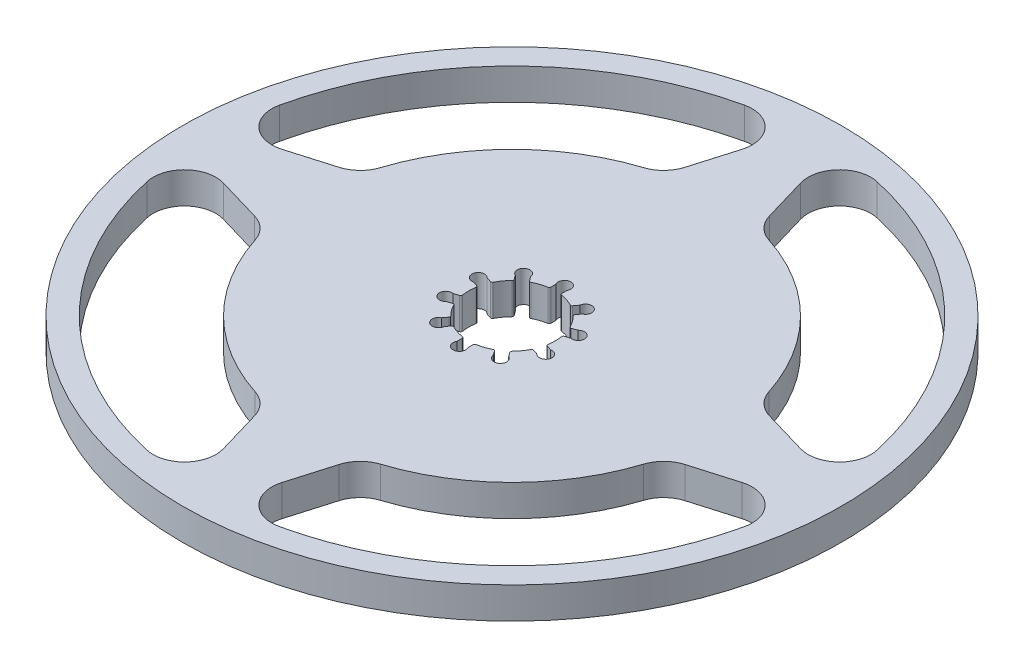
SolidWorks part; units mm, degrees
material "Alum Plate"
ref_plane "Front Plane" through (0, 0, 0) normal (0, 0, 1) x (1, 0, 0)
ref_plane "Top Plane" through (0, 0, 0) normal (0, 1, 0) x (1, 0, 0)
ref_plane "Right Plane" through (0, 0, 0) normal (1, 0, 0) x (0, 0, -1)
other "Center of Mass"
other "Bounding Box"
ref_plane "Default Plane" through (0, 2.286, 19.05) normal (0, -1, 0) x (-1, 0, 0)
sketch "Sketch1" plane through (0, 0, 0) normal (0, 1, 0) x (1, 0, 0)
  circle A0 centre (0, 0) radius 133.35 construction
  circle A1 centre (0, 0) radius 82.55
  circle A2 centre (0, 0) radius 17.4625
  dimension "D1" = 266.7
  dimension "D2" = 165.1
  dimension "D3" = 34.925
extrude "Boss-Extrude1" add sketch "Sketch1" along normal mid plane 12.7
sketch "Sketch8" plane through (0, 6.35, 0) normal (0, 1, 0) x (1, 0, 0)
  circle A0 centre (0, 0) radius 123.825
  circle A1 centre (0, 0) radius 133.35
  circle A2 centre (0, 0) radius 133.35 construction
  dimension "D1" = 9.525
extrude "Boss-Extrude4" add sketch "Sketch8" against normal through all
sketch "Sketch2" plane through (0, 6.35, 0) normal (0, 1, 0) x (1, 0, 0)
  line L4 (0, 0) -> (0, 133.35) construction
  line L6 (-6.35, 123.6621) -> (6.35, 123.6621) construction
  line L7 (-6.35, 123.6621) -> (-19.05, 80.3219)
  line L8 (-19.05, 80.3219) -> (19.05, 80.3219)
  line L9 (6.35, 123.6621) -> (19.05, 80.3219)
  line L10 (-6.35, 123.6621) -> (19.05, 80.3219) construction
  line L11 (-19.05, 80.3219) -> (6.35, 123.6621) construction
  circle A5 centre (0, 0) radius 133.35 construction
  circle A7 centre (0, 0) radius 82.55 construction
  arc A9 (-6.35, 123.6621) -> (6.35, 123.6621) centre (0, 0) cw
  circle A10 centre (0, 0) radius 123.825 construction
  point P4 (0, 112.827)
  point P6 (13.7165, 123.0629)
  point P11 (-14.1161, 122.0628)
  point P13 (6.9138, 120.4517)
  dimension "D1" = 38.1
  dimension "D2" = 12.7
extrude "Boss-Extrude2" add sketch "Sketch2" against normal through all
fillet "Fillet7" radius 12.7 4 edges at (-6.35, 0, -123.6621) (-19.05, 0, -80.3219) (19.05, 0, -80.3219) (6.35, 0, -123.6621)
pattern_circular "CirPattern5" count 4 over 360 about axis through (0, 6.35, 0) along (0, -1, 0) of "Boss-Extrude2", "Fillet7"
sketch "Sketch5" plane through (0, 6.35, 0) normal (0, 1, 0) x (1, 0, 0)
  line L0 (0, 17.4625) -> (0, 21.2725) construction
  line L2 (-2.2225, 17.3205) -> (2.2225, 17.3205)
  line L3 (-2.2225, 17.3205) -> (-2.2225, 20.0168)
  line L5 (2.2225, 17.3205) -> (2.2225, 20.0168)
  arc A0 (2.2225, 20.0168) -> (-2.2225, 20.0168) centre (0, 21.2725) ccw
  circle A1 centre (0, 0) radius 17.4625 construction
  circle A2 centre (0, 21.2725) radius 4.5847 construction
  dimension "D2" = 5.1054
  dimension "D4" = 9.1694
  dimension "D1" = 3.81
  dimension "D3" = 4.445
extrude "Cut-Extrude2" cut sketch "Sketch5" against normal through all
pattern_circular "CirPattern1" count 10 over 360 about axis through (0, 6.35, 0) along (0, -1, 0) of "Cut-Extrude2"
sketch "Sketch6" plane through (0, 6.35, 0) normal (0, 1, 0) x (1, 0, 0)
  circle A0 centre (0, 0) radius 17.526
  arc A1 (-11.9788, 12.7062) -> (-15.786, 7.466) centre (0, 0) ccw construction
  dimension "D1" = 0.0635
extrude "Cut-Extrude3" cut sketch "Sketch6" against normal through all
fillet "Fillet6" radius 0.635 20 edges at (-12.0164, 0, -12.758) (-15.8469, 0, -7.4858) (-17.2204, 0, -3.2584) (-17.2204, 0, 3.2584) (-15.8469, 0, 7.4858) (-12.0164, 0, 12.758) (-8.4203, 0, 15.3707) (-2.2225, 0, 17.3845) (2.2225, 0, 17.3845) (8.4203, 0, 15.3707) (12.0164, 0, 12.758) (15.8469, 0, 7.4858) (17.2204, 0, 3.2584) (17.2204, 0, -3.2584) (15.8469, 0, -7.4858) (12.0164, 0, -12.758) (8.4203, 0, -15.3707) (2.2225, 0, -17.3845) (-2.2225, 0, -17.3845) (-8.4203, 0, -15.3707)
equation "\"Unit Measure\"= \"BoundingVolume\" / \"Thickness\"'in^2"
